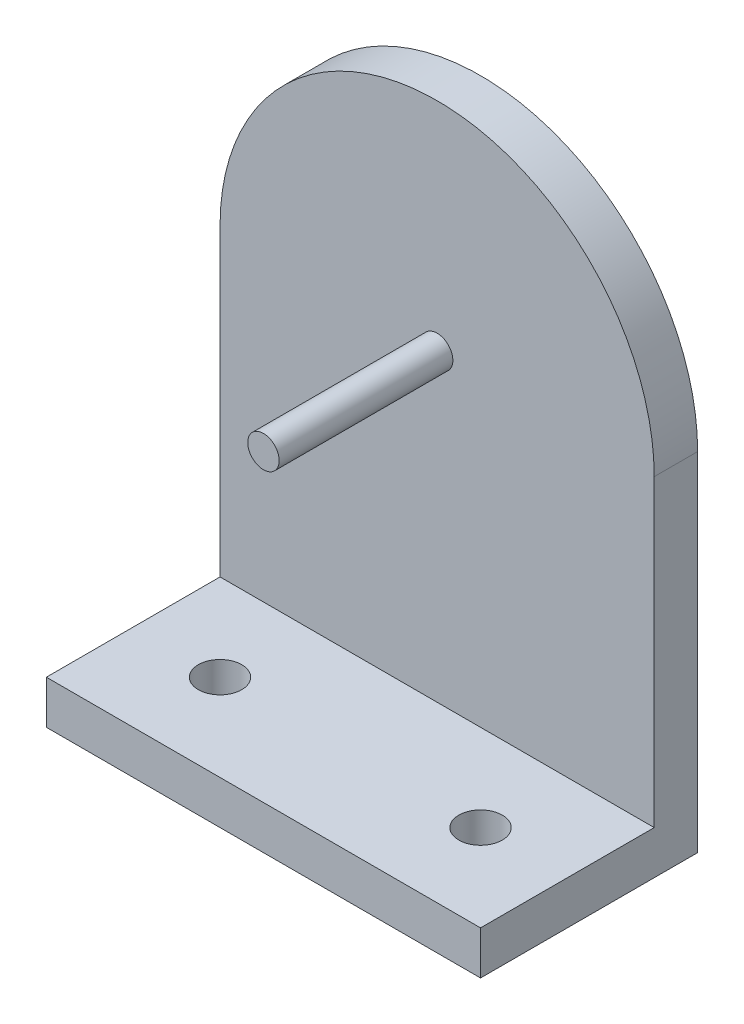
SolidWorks part; units mm, degrees
ref_plane "Front Plane" through (0, 0, 0) normal (0, 0, 1) x (1, 0, 0)
ref_plane "Top Plane" through (0, 0, 0) normal (0, 1, 0) x (1, 0, 0)
ref_plane "Right Plane" through (0, 0, 0) normal (1, 0, 0) x (0, 0, -1)
sketch "Sketch1" plane through (0, 0, 0) normal (0, 0, 1) x (1, 0, 0)
  line L1 (-15.875, 0) -> (15.875, 0)
  line L2 (-15.875, 0) -> (-15.875, -25.4)
  line L3 (-15.875, -25.4) -> (15.875, -25.4)
  line L4 (15.875, 0) -> (15.875, -25.4)
  circle A0 centre (0, 0) radius 15.875
  arc A2 (-15.875, 0) -> (15.875, 0) centre (0, 0) ccw
  dimension "D1" = 31.75
  dimension "D2" = 25.4
extrude "Boss-Extrude1" add sketch "Sketch1" along normal blind 3.175 contours A0 | L2 L1 L4 L3
sketch "Sketch4" plane through (0, 0, 3.175) normal (0, 0, 1) x (1, 0, 0)
  line L0 (15.875, 0) -> (15.875, -25.4) construction
  line L1 (-15.875, -25.4) -> (15.875, -25.4)
  line L2 (-15.875, -25.4) -> (-15.875, -22.225)
  line L3 (-15.875, -22.225) -> (15.875, -22.225)
  line L4 (15.875, -25.4) -> (15.875, -22.225)
  dimension "D1" = 3.175
extrude "Boss-Extrude2" add sketch "Sketch4" along normal blind 12.7
sketch "Sketch5" plane through (0, -22.225, 0) normal (0, 1, 0) x (1, 0, 0)
  line L0 (-15.875, -9.525) -> (15.875, -9.525) construction
  line L1 (-15.875, -15.875) -> (-15.875, -3.175) construction
  line L2 (15.875, -15.875) -> (15.875, -3.175) construction
  line L3 (0, -3.175) -> (0, -15.875) construction
  line L4 (15.875, -3.175) -> (-15.875, -3.175) construction
  line L5 (15.875, -15.875) -> (-15.875, -15.875) construction
  circle A0 centre (-9.525, -9.525) radius 1.5875
  circle A1 centre (9.525, -9.525) radius 1.5875
  dimension "D1" = 3.175
  dimension "D2" = 9.525
extrude "Cut-Extrude2" cut sketch "Sketch5" against normal through all
sketch "Sketch6" plane through (0, 0, 3.175) normal (0, 0, 1) x (1, 0, 0)
  circle A0 centre (0, 0) radius 1.15
  dimension "D1" = 2.3
extrude "Boss-Extrude3" add sketch "Sketch6" along normal through all
